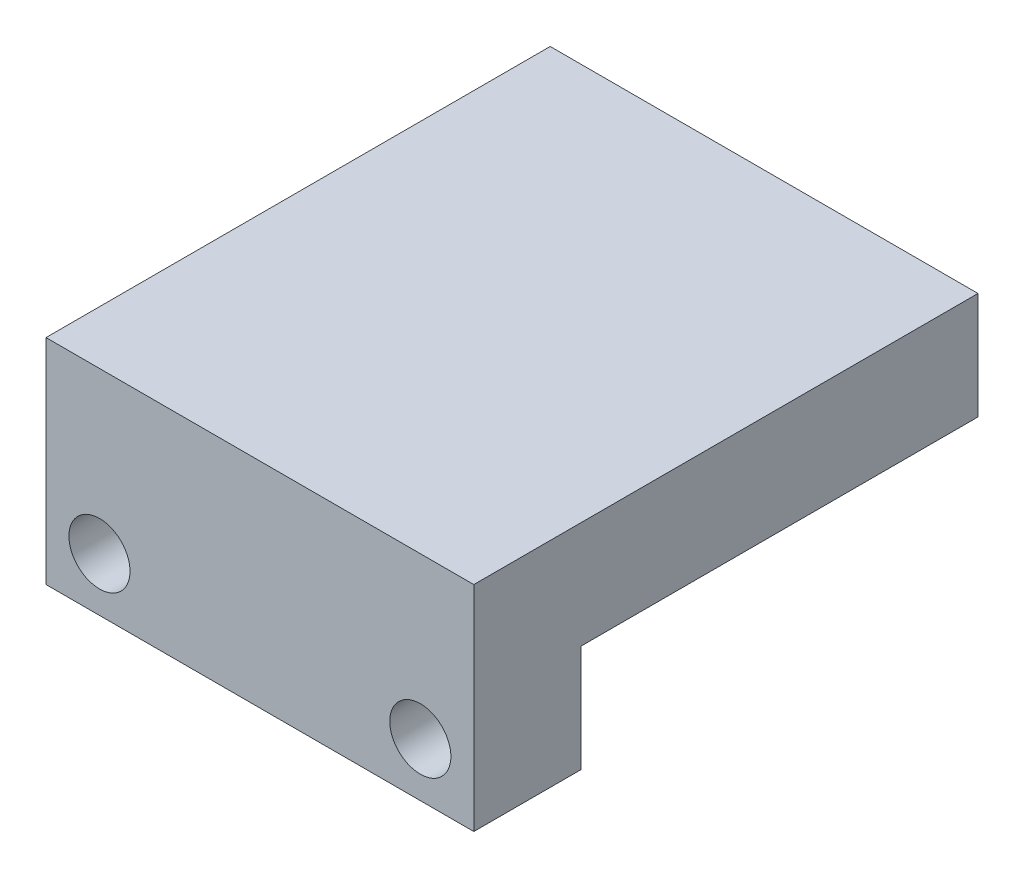
SolidWorks part; units mm, degrees
ref_plane "Front Plane" through (0, 0, 0) normal (0, 0, 1) x (1, 0, 0)
ref_plane "Top Plane" through (0, 0, 0) normal (0, 1, 0) x (1, 0, 0)
ref_plane "Right Plane" through (0, 0, 0) normal (1, 0, 0) x (0, 0, -1)
sketch "Sketch1" plane through (0, 0, 0) normal (0, 1, 0) x (1, 0, 0)
  line L1 (-14, 14) -> (14, 14)
  line L2 (-14, 14) -> (-14, -14)
  line L3 (-14, -14) -> (14, -14)
  line L4 (14, 14) -> (14, -14)
  line L5 (-14, 14) -> (14, -14) construction
  line L6 (-14, -14) -> (14, 14) construction
  line L7 (-14, -14) -> (14, -14)
  line L8 (-14, -14) -> (-14, -19)
  line L9 (-14, -19) -> (14, -19)
  line L10 (14, -14) -> (14, -19)
  circle A0 centre (0, 0) radius 9
  point P0 (0, 0)
  dimension "D1" = 18
  dimension "D2" = 5
  dimension "D3" = 5
extrude "Boss-Extrude3" add sketch "Sketch1" against normal blind 5 contours L4 L1 L2 L3 A0 region at (0, 0, -13.604)
extrude "Boss-Extrude4" add sketch "Sketch1<4>" along normal blind 2 contours L4 L1 L2 L3 A0 | L10 L3 L8 L9 | A0 region at (0, 0, -13.604) region at (0, 0, 16.5) region at (0, 0, 0)
sketch "Sketch1<4>" plane through (0, 0, 0) normal (0, 1, 0) x (1, 0, 0) same geometry as "Sketch1"
extrude "Boss-Extrude5" add sketch "Sketch1<5>" against normal blind 12 contours L10 L3 L8 L9 region at (0, 0, 16.5)
sketch "Sketch1<5>" plane through (0, 0, 0) normal (0, 1, 0) x (1, 0, 0) same geometry as "Sketch1"
sketch "Sketch2" plane through (0, 0, 14) normal (0, 0, -1) x (-1, 0, 0)
  line L0 (-14, -12) -> (-7, -5) construction
  line L1 (0, -5) -> (0, -12) construction
  line L4 (14, -12) -> (14, -5)
  line L5 (14, -5) -> (-14, -5)
  line L6 (-14, -5) -> (-14, -12)
  line L7 (-14, -12) -> (14, -12)
  line L8 (14, -12) -> (14, -5)
  line L9 (14, -5) -> (-14, -5)
  line L10 (-14, -5) -> (-14, -12)
  line L11 (-14, -12) -> (14, -12)
  circle A0 centre (-10.5, -8.5) radius 2
  circle A1 centre (10.5, -8.5) radius 2
  dimension "D3" = 4
  dimension "D2" = 45
extrude "Cut-Extrude1" cut sketch "Sketch2" against normal through all contours A0 | A1 region at (10.5, -8.5, 14) region at (-10.5, -8.5, 14)
extrude "Boss-Extrude6" add sketch "Sketch2<3>" along normal blind 2
sketch "Sketch2<3>" plane through (0, 0, 14) normal (0, 0, -1) x (-1, 0, 0) same geometry as "Sketch2"
equation "\"d\"= 18"
equation "\"h\"= 5"
equation "\"sd\"= 4"
equation "\"D1@Sketch1\"=\"d\""
equation "\"D3@Sketch2\"=\"sd\""
